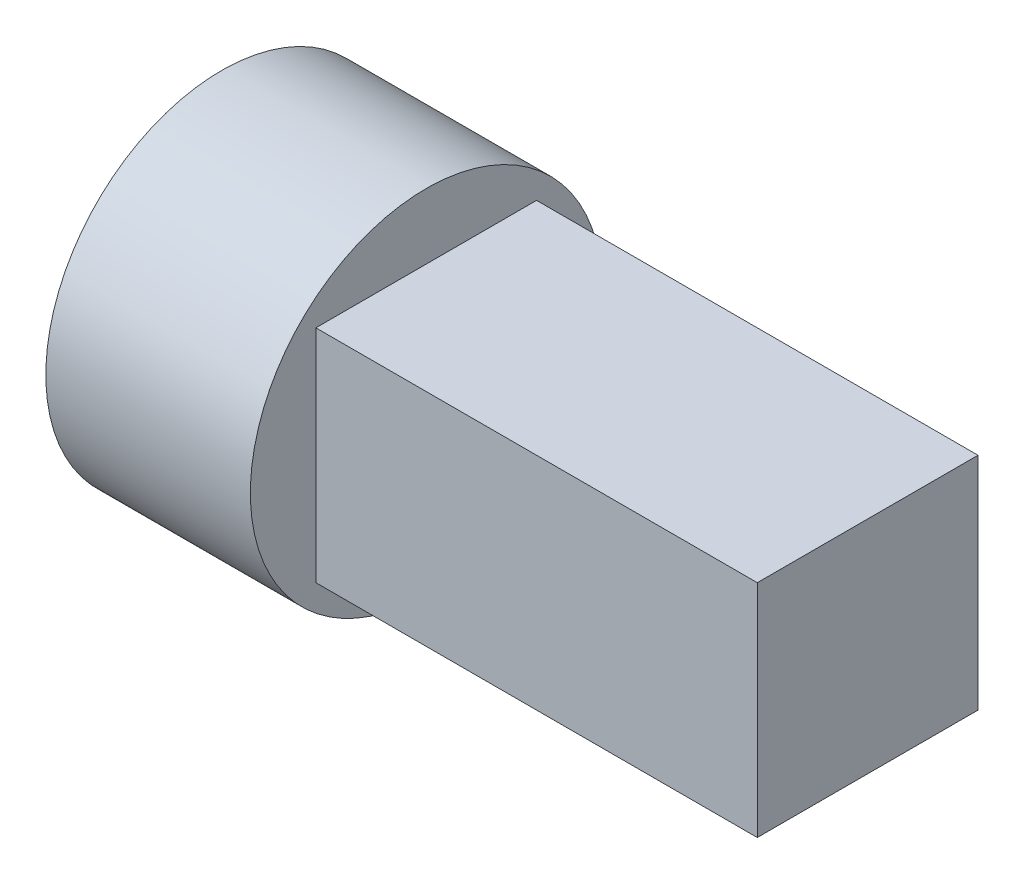
SolidWorks part; units mm, degrees
ref_plane "Front Plane" through (0, 0, 0) normal (0, 0, 1) x (1, 0, 0)
ref_plane "Top Plane" through (0, 0, 0) normal (0, 1, 0) x (1, 0, 0)
ref_plane "Right Plane" through (0, 0, 0) normal (1, 0, 0) x (0, 0, -1)
sketch "Sketch1" plane through (0, 0, 0) normal (1, 0, 0) x (0, 0, -1)
  circle A0 centre (0, 0) radius 4.78
  dimension "D1" = 9.56
extrude "Boss-Extrude1" add sketch "Sketch1" along normal mid plane 5.56
sketch "Sketch2" plane through (2.78, 0, 0) normal (1, 0, 0) x (0, 0, -1)
  line L1 (-3, 3) -> (3, 3)
  line L2 (-3, 3) -> (-3, -3)
  line L3 (-3, -3) -> (3, -3)
  line L4 (3, 3) -> (3, -3)
  line L5 (-3, 3) -> (3, -3) construction
  line L6 (-3, -3) -> (3, 3) construction
  point P0 (0, 0)
  dimension "D1" = 6
extrude "Boss-Extrude2" add sketch "Sketch2" along normal blind 12
